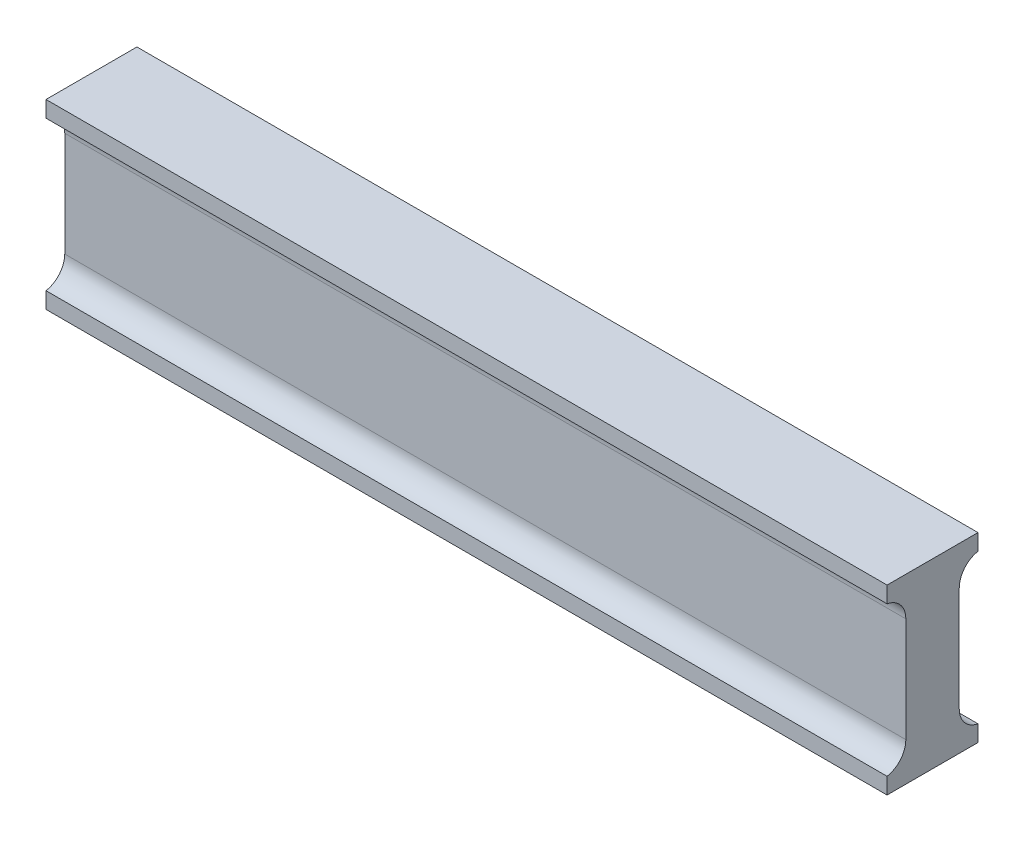
SolidWorks part; units mm, degrees
material "ABS"
ref_plane "Alzado" through (0, 0, 0) normal (0, 0, 1) x (1, 0, 0)
ref_plane "Planta" through (0, 0, 0) normal (0, 1, 0) x (1, 0, 0)
ref_plane "Vista lateral" through (0, 0, 0) normal (1, 0, 0) x (0, 0, -1)
sketch "Sketch1" plane through (0, 0, 0) normal (0, 0, 1) x (1, 0, 0)
  line L1 (-92.5, -20) -> (92.5, -20)
  line L2 (-92.5, -20) -> (-92.5, 20)
  line L3 (-92.5, 20) -> (92.5, 20)
  line L4 (92.5, -20) -> (92.5, 20)
  line L5 (-92.5, -20) -> (92.5, 20) construction
  line L6 (-92.5, 20) -> (92.5, -20) construction
  point P0 (0, 0)
  dimension "D1" = 185
  dimension "D2" = 40
extrude "Boss-Extrude1" add sketch "Sketch1" along normal blind 20
sketch "Sketch2" plane through (92.5, 0, 0) normal (1, 0, 0) x (0, 0, -1)
  line L0 (-10, -1020) -> (-10, 48980) construction
  line L1 (-20, -20) -> (0, -20) construction
  line L2 (-24.125, -16.427) -> (-15.875, -16.427)
  line L3 (4.125, -16.427) -> (-4.125, -16.427)
  line L4 (4.125, -16.427) -> (4.125, 16.427)
  line L5 (4.125, 16.427) -> (-4.125, 16.427)
  line L6 (-4.125, -16.427) -> (-4.125, 16.427)
  line L7 (4.125, -16.427) -> (-4.125, 16.427) construction
  line L8 (4.125, 16.427) -> (-4.125, -16.427) construction
  line L9 (-15.875, -16.427) -> (-15.875, 16.427)
  line L10 (-24.125, 16.427) -> (-15.875, 16.427)
  line L11 (-24.125, -16.427) -> (-24.125, 16.427)
  point P1 (0, 0)
  point P5 (-10, -20)
extrude "Cut-Extrude1" cut sketch "Sketch2" against normal through all
fillet "Fillet1" radius 5 4 edges at (0, 16.427, 4.125) (0, -16.427, 4.125) (0, -16.427, 15.875) (0, 16.427, 15.875)
